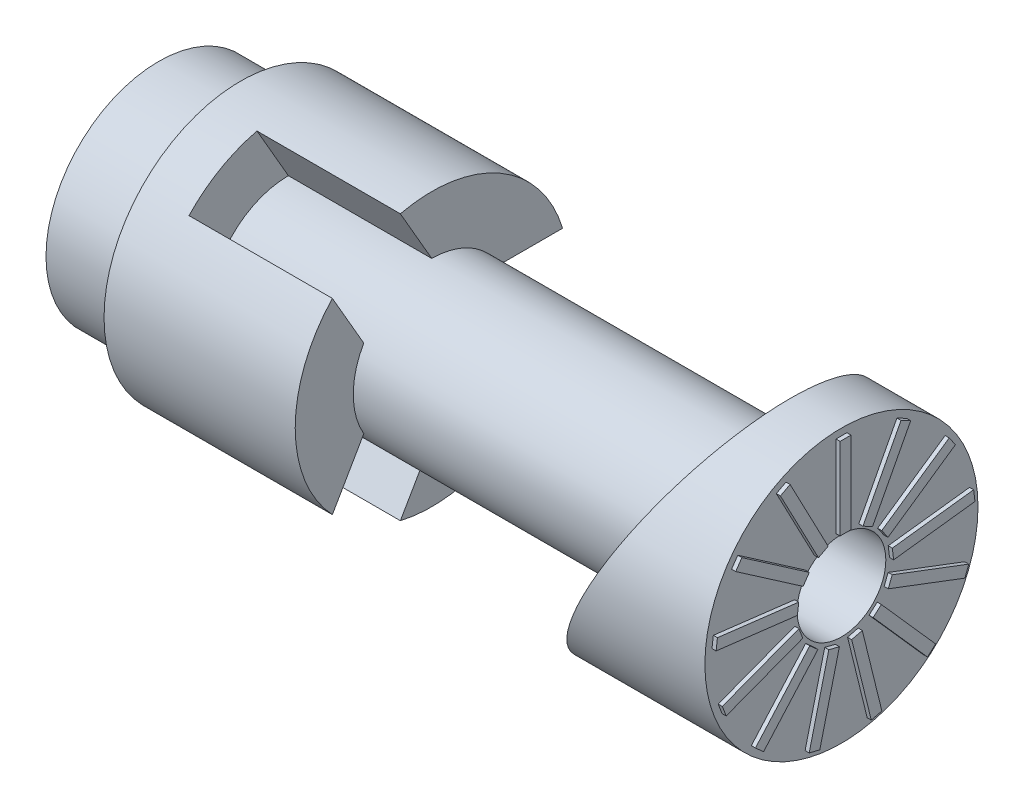
SolidWorks part; units mm, degrees
ref_plane "前视基准面" through (0, 0, 0) normal (0, 0, 1) x (1, 0, 0)
ref_plane "上视基准面" through (0, 0, 0) normal (0, 1, 0) x (1, 0, 0)
ref_plane "右视基准面" through (0, 0, 0) normal (1, 0, 0) x (0, 0, -1)
other "Configuration Table"
sketch "草图1" plane through (0, 0, 0) normal (0, 0, 1) x (1, 0, 0)
  line L0 (0, 0) -> (0, -8.25)
  line L1 (0, -8.25) -> (6, -8.25)
  line L2 (6, -10) -> (6, -8.25)
  line L3 (6, -10) -> (20, -10)
  line L4 (20, -10) -> (20, -5.75)
  line L5 (20, -5.75) -> (36, -5.75)
  line L6 (36, -5.75) -> (36, -10)
  line L7 (36, -10) -> (50, -10)
  line L8 (50, -10) -> (50, 0)
  line L9 (50, 0) -> (0, 0) construction
  line L10 (36, -5.75) -> (36, 0)
  dimension "D1" = 50
  dimension "D2" = 20
  dimension "D3" = 16.5
  dimension "D4" = 6
  dimension "D5" = 30
  dimension "D6" = 14
  dimension "D7" = 11.5
revolve "旋转1" add sketch "草图1" angle 360 about L9 region at (16.1439, -4.1516, 0)
sketch "草图2" plane through (20, 0, 0) normal (1, 0, 0) x (0, 0, -1)
  line L0 (5.75, 0) -> (10, 0) construction
  line L1 (4.9796, 2.875) -> (9.5778, 2.875)
  line L2 (0, -5.75) -> (-2.2991, -9.7321)
  line L3 (9.5778, -2.875) -> (4.9796, -2.875)
  line L4 (-7.2787, -6.8571) -> (-4.9796, -2.875)
  line L5 (-4.9796, 2.875) -> (-7.2787, 6.8571)
  line L6 (-2.2991, 9.7321) -> (0, 5.75)
  circle A0 centre (0, 0) radius 5.75 construction
  circle A1 centre (0, 0) radius 10
  circle A2 centre (0, 0) radius 10
  circle A3 centre (0, 0) radius 5.75
  point P23 (0, 0)
  circle M9 centre (0, 0) radius 5.75
  circle M10 centre (0, 0) radius 10
  dimension "D2" = 5.75
  dimension "D1" = 0
  dimension "D3" = 3
extrude "切除-拉伸1" cut sketch "草图2" against normal blind 10.5 contours L6 L5 M10 M9 | L4 L2 M10 M9 | L0 A3 L3 M10 | L0 A2 L1 M9 region at (20, 1.4561, -7.6764) region at (20, -1.4561, -7.6764) region at (20, 6.6479, 3.8382) region at (20, -6.6479, 3.8382)
revolve "旋转2" add sketch "草图1<3>" angle 360 about L9 region at (43, -5, 0)
sketch "草图1<3>" plane through (0, 0, 0) normal (0, 0, 1) x (1, 0, 0) same geometry as "草图1"
sketch "草图3" plane through (0, 0, 0) normal (0, 0, 1) x (1, 0, 0)
  line L0 (36, -10) -> (36, 10)
  line L1 (36, 10) -> (36, -10) construction
  line L2 (36, 10) -> (46.25, 10)
  line L3 (50, 10) -> (36, 10) construction
  line L4 (46.25, 10) -> (36, -10)
  line L5 (50, -10) -> (50, 10) construction
  dimension "D1" = 3.75
extrude "切除-拉伸2" cut sketch "草图3" against normal through all both and the other way through all
sketch "草图4" plane through (36, 0, 0) normal (1, 0, 0) x (0, 0, -1)
  circle A1 centre (0, 0) radius 5.75
  circle A2 centre (0, 0) radius 5.75
  dimension "D1" = 0
extrude "凸台-拉伸1" add sketch "草图4" along normal up to next
sketch "草图5" plane through (50, 0, 0) normal (1, 0, 0) x (0, 0, -1)
  circle A0 centre (0, 0) radius 3.25
  dimension "D1" = 6.5
extrude "切除-拉伸3" cut sketch "草图5" against normal through all
sketch "草图6" plane through (50, 0, 0) normal (1, 0, 0) x (0, 0, -1)
  line L1 (-0.4, 9.5) -> (0.4, 9.5)
  line L2 (-0.4, 9.5) -> (-0.4, 3.5)
  line L3 (-0.4, 3.5) -> (0.4, 3.5)
  line L4 (0.4, 9.5) -> (0.4, 3.5)
  line L5 (-0.4, 9.5) -> (0.4, 3.5) construction
  line L6 (-0.4, 3.5) -> (0.4, 9.5) construction
  point P0 (0, 6.5)
  dimension "D1" = 0.8
  dimension "D2" = 6
  dimension "D3" = 3.5
extrude "凸台-拉伸2" add sketch "草图6" along normal blind 0.3
pattern_circular "阵列(圆周)1" count 13 over 360 about axis through (0, 0, 0) along (1, 0, 0) of "凸台-拉伸2"
